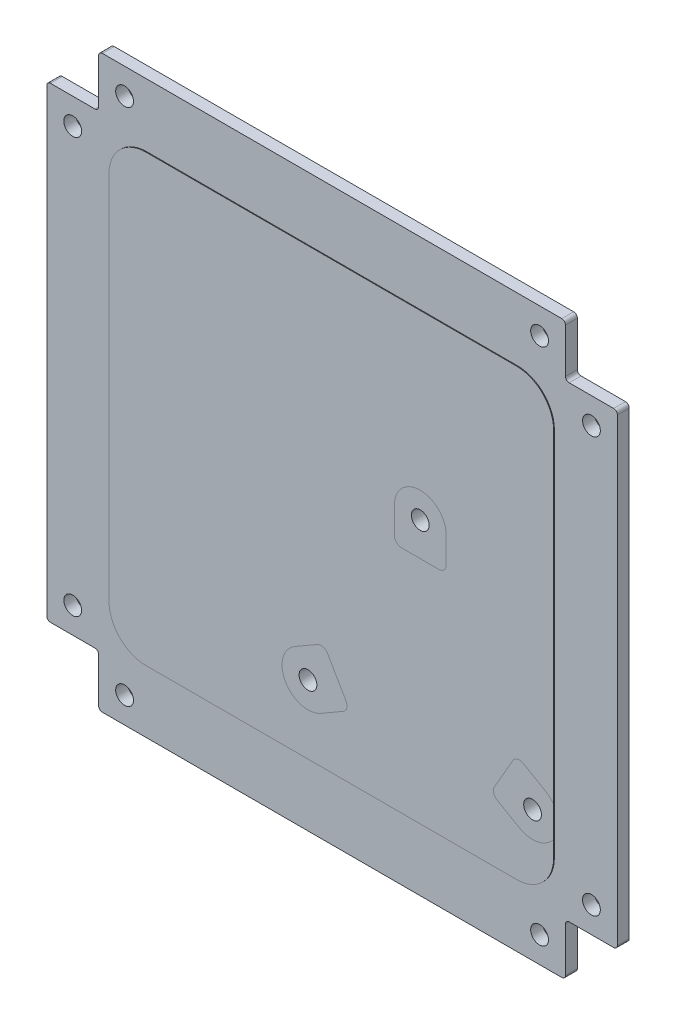
SolidWorks part; units mm, degrees
material "PET"
ref_plane "Front Plane" through (0, 0, 0) normal (0, 0, 1) x (1, 0, 0)
ref_plane "Top Plane" through (0, 0, 0) normal (0, 1, 0) x (1, 0, 0)
ref_plane "Right Plane" through (0, 0, 0) normal (1, 0, 0) x (0, 0, -1)
sketch "Sketch1" plane through (0, 0, 0) normal (0, 0, 1) x (1, 0, 0)
  line L0 (-31.5, 38) -> (-31.5, 32)
  line L1 (-31, -38.5) -> (31, -38.5)
  line L2 (-38.5, 31) -> (-38.5, -31)
  line L3 (-31, 38.5) -> (31, 38.5)
  line L4 (38.5, -31) -> (38.5, 31)
  line L5 (31.5, -38) -> (31.5, -32)
  line L6 (32, -31.5) -> (38, -31.5)
  line L7 (-32, 31.5) -> (-38, 31.5)
  line L8 (31.5, 38) -> (31.5, 32)
  line L9 (32, 31.5) -> (38, 31.5)
  line L10 (-38, -31.5) -> (-32, -31.5)
  line L11 (-31.5, -32) -> (-31.5, -38)
  line L12 (-32, -32) -> (32, 32) construction
  line L13 (32, -32) -> (-32, 32) construction
  arc A0 (-31, 38.5) -> (-31.5, 38) centre (-31, 38) ccw
  arc A1 (31, 38.5) -> (31.5, 38) centre (31, 38) cw
  arc A2 (31.5, 32) -> (32, 31.5) centre (32, 32) ccw
  arc A3 (38, 31.5) -> (38.5, 31) centre (38, 31) cw
  arc A4 (31, -38.5) -> (31.5, -38) centre (31, -38) ccw
  arc A5 (32, -31.5) -> (31.5, -32) centre (32, -32) ccw
  arc A6 (38, -31.5) -> (38.5, -31) centre (38, -31) ccw
  arc A7 (-31.5, -38) -> (-31, -38.5) centre (-31, -38) ccw
  arc A8 (-31.5, -32) -> (-32, -31.5) centre (-32, -32) ccw
  arc A9 (-38.5, -31) -> (-38, -31.5) centre (-38, -31) ccw
  arc A10 (-38, 31.5) -> (-38.5, 31) centre (-38, 31) ccw
  arc A11 (-32, 31.5) -> (-31.5, 32) centre (-32, 32) ccw
  point P0 (0, 0)
  dimension "D4" = 0.5
  dimension "D1" = 7
  dimension "D2" = 7
  dimension "D3" = 7
  dimension "D5" = 7
  dimension "D6" = 7
  dimension "D7" = 7
  dimension "D8" = 7
  dimension "D9" = 7
  dimension "D10" = 77
  dimension "D11" = 77
extrude "Boss-Extrude1" add sketch "Sketch1" along normal blind 1.6
sketch "Esboço1" plane through (0, 0, 1.6) normal (0, 0, 1) x (1, 0, 0)
  line L1 (-25, -30) -> (25, -30)
  line L2 (-30, -25) -> (-30, 25)
  line L3 (-25, 30) -> (25, 30)
  line L4 (30, -25) -> (30, 25)
  line L5 (-25, -25) -> (25, 25) construction
  line L6 (-25, 25) -> (25, -25) construction
  arc A0 (-30, 25) -> (-25, 30) centre (-25, 25) cw
  arc A1 (25, 30) -> (30, 25) centre (25, 25) cw
  arc A2 (30, -25) -> (25, -30) centre (25, -25) cw
  arc A3 (-25, -30) -> (-30, -25) centre (-25, -25) cw
  point P0 (0, 0)
  dimension "D1" = 5
  dimension "D2" = 60
  dimension "D3" = 60
extrude "Boss-Extrude2" add sketch "Esboço1" along normal blind 0.1
hole_wizard "M2 Hole1-FixingStructure" positions "Sketch3" profile "Sketch2" hole size "M2" standard "DIN"
sketch "Sketch3" plane through (0, 0, 0) normal (0, 0, -1) x (-1, 0, 0)
  line L0 (-31, 38.5) -> (31, 38.5) construction
  line L1 (31, -38.5) -> (-31, -38.5) construction
  line L2 (-38.5, -31) -> (-38.5, 31) construction
  line L3 (38.5, 31) -> (38.5, -31) construction
  line L4 (-31, 38.5) -> (31, 38.5) construction
  line L5 (31, -38.5) -> (-31, -38.5) construction
  line L6 (38.5, 31) -> (38.5, -31) construction
  line L7 (-38.5, -31) -> (-38.5, 31) construction
  point P0 (-28, 35)
  point P2 (28, 35)
  point P4 (-28, -35)
  point P6 (28, -35)
  point P20 (35, 28)
  point P22 (35, -28)
  point P24 (-35, -28)
  point P26 (-35, 28)
  dimension "D1" = 3.5
  dimension "D2" = 3.5
  dimension "D3" = 10.5
  dimension "D4" = 10.5
  dimension "D5" = 10.5
  dimension "D6" = 10.5
  dimension "D7" = 3.5
  dimension "D8" = 3.5
sketch "Sketch2" plane through (28, 35, 0) normal (1, 0, 0) x (0, 1, 0)
  line L0 (0, 0) -> (0, 200.721)
  line L1 (0, 200.721) -> (1.2, 200)
  line L2 (1.2, 200) -> (1.2, 0)
  line L5 (1.2, 0) -> (0, 0)
  line L10 (0, 200.721) -> (-1.2, 200) construction
  line L11 (0, -6.35) -> (0, 107.95) construction
  dimension "Hole Dia." = 2.4
  dimension "Hole Depth" = 200
  dimension "Drill Angle" = 118
sketch "Sketch5" plane through (0, 0, 1.7) normal (0, 0, 1) x (1, 0, 0)
  circle A0 centre (-3.1554, -20.75) radius 1.2 construction
  circle A1 centre (27.1554, -20.75) radius 1.2 construction
  circle A2 centre (12, 5.5) radius 1.2 construction
  circle A3 centre (-3.1554, -20.75) radius 1.2
  circle A4 centre (27.1554, -20.75) radius 1.2
  circle A5 centre (12, 5.5) radius 1.2
extrude "Cut-Extrude1" cut sketch "Sketch5" against normal up to surface (1.7 mm away) up to face at (26.8, 35, 0)
sketch "Sketch6" plane through (0, 0, 1.7) normal (0, 0, 1) x (1, 0, 0)
  line L0 (1.6256, -22.0311) -> (-1.4054, -23.7811)
  line L1 (-4.9054, -17.7189) -> (-1.8744, -15.9689)
  line L2 (-0.5083, -16.3349) -> (1.9917, -20.6651)
  line L3 (8.5, 2) -> (8.5, 5.5)
  line L4 (15.5, 5.5) -> (15.5, 2)
  line L5 (14.5, 1) -> (9.5, 1)
  line L6 (26.7404, -16.4689) -> (28.9054, -17.7189)
  line L7 (25.4054, -23.7811) -> (23.2404, -22.5311)
  line L8 (25.8744, -15.9689) -> (28.9054, -17.7189)
  line L9 (25.4054, -23.7811) -> (22.3744, -22.0311)
  line L10 (22.0083, -20.6651) -> (24.5083, -16.3349)
  line L11 (22.0083, -20.6651) -> (24.5083, -16.3349)
  arc A0 (1.6256, -22.0311) -> (1.9917, -20.6651) centre (1.1256, -21.1651) ccw
  arc A1 (-4.9054, -17.7189) -> (-1.4054, -23.7811) centre (-3.1554, -20.75) ccw
  arc A2 (25.8744, -15.9689) -> (24.5083, -16.3349) centre (25.3744, -16.8349) ccw
  arc A3 (25.4054, -23.7811) -> (28.9054, -17.7189) centre (27.1554, -20.75) ccw
  arc A4 (25.4054, -23.7811) -> (28.9054, -17.7189) centre (27.1554, -20.75) ccw
  arc A5 (22.3744, -22.0311) -> (22.0083, -20.6651) centre (22.8744, -21.1651) cw
  circle A6 centre (12, -12) radius 4.4 construction
  arc A7 (-1.8744, -15.9689) -> (-0.5083, -16.3349) centre (-1.3744, -16.8349) cw
  arc A8 (8.5, 2) -> (9.5, 1) centre (9.5, 2) ccw
  arc A9 (15.5, 5.5) -> (8.5, 5.5) centre (12, 5.5) ccw
  arc A10 (15.5, 2) -> (14.5, 1) centre (14.5, 2) cw
  point P13 (12, -12)
  point P36 (12, -12)
  dimension "D3" = 1
  dimension "D1" = 1
  dimension "D2" = 1
  dimension "D4" = 3
split line "Split Line1"
